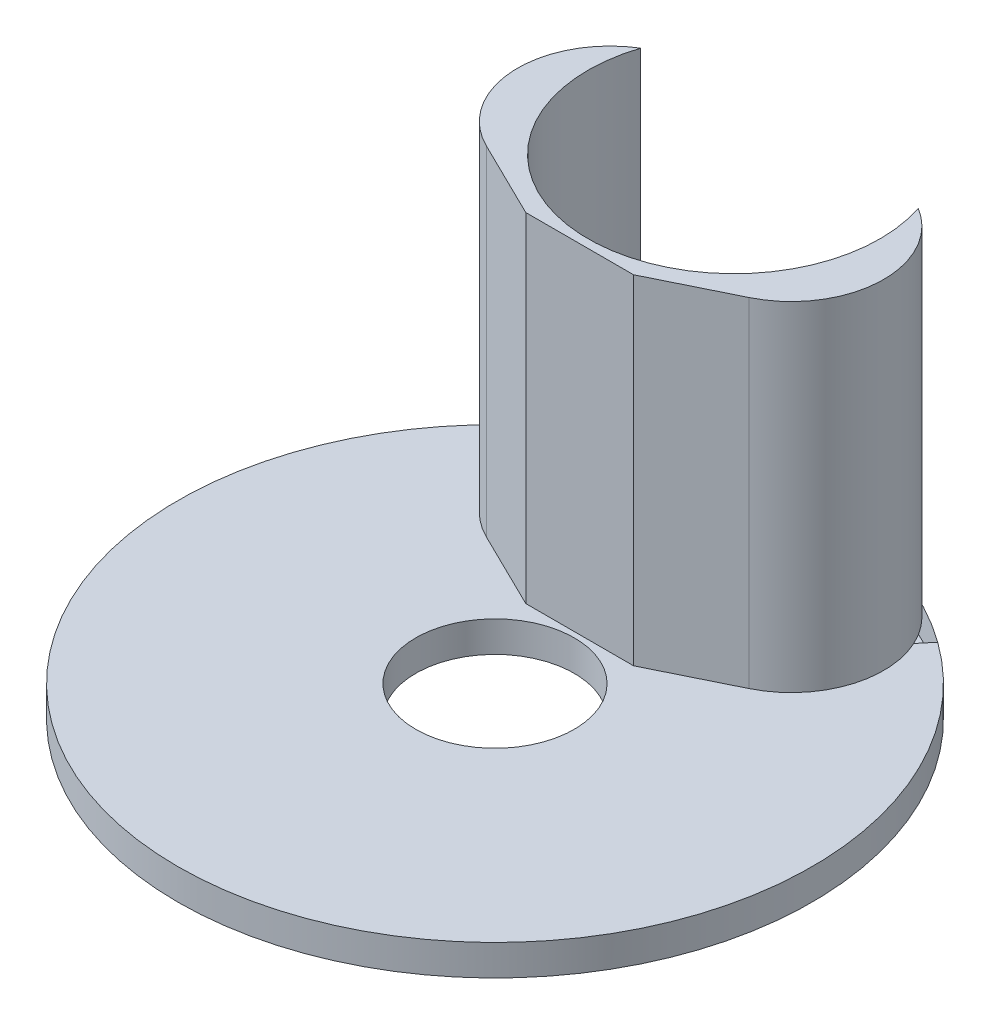
SolidWorks part; units mm, degrees
ref_plane "Front Plane" through (0, 0, 0) normal (0, 0, 1) x (1, 0, 0)
ref_plane "Top Plane" through (0, 0, 0) normal (0, 1, 0) x (1, 0, 0)
ref_plane "Right Plane" through (0, 0, 0) normal (1, 0, 0) x (0, 0, -1)
sketch "Sketch1" plane through (0, 0, 0) normal (0, 1, 0) x (1, 0, 0)
  circle A0 centre (0, 0) radius 20.6
  dimension "D1" = 41.2
extrude "Boss-Extrude1" add sketch "Sketch1" along normal blind 2
sketch "Sketch2" plane through (0, 2, 0) normal (0, 1, 0) x (1, 0, 0)
  circle A0 centre (0, 0) radius 5.15
  dimension "D1" = 10.3
extrude "Cut-Extrude1" cut sketch "Sketch2" against normal blind 3
sketch "Sketch3" plane through (0, 2, 0) normal (0, 1, 0) x (1, 0, 0)
  circle A0 centre (0, 13) radius 6.5
  dimension "D2" = 13
  dimension "D1" = 13
extrude "Cut-Extrude2" cut sketch "Sketch3" against normal blind 2
sketch "Sketch4" plane through (0, 2, 0) normal (0, 1, 0) x (1, 0, 0)
  line L0 (-3.5, 5.5) -> (-16.744, 12)
  line L1 (3.5, 5.5) -> (16.744, 12)
  line L4 (-3.5, 5.5) -> (3.5, 5.5)
  arc A0 (-16.744, 12) -> (-9, 18.53) centre (0, 0) cw
  circle A1 centre (0, 0) radius 20.6 construction
  arc A4 (9, 18.53) -> (16.744, 12) centre (0, 0) cw
  arc A6 (-9, 18.53) -> (9, 18.53) centre (0, 15.5297) ccw
  circle M8 centre (0, 0) radius 20.6
  dimension "D1" = 12
  dimension "D2" = 12
  dimension "D3" = 5.5
  dimension "D4" = 5.5
  dimension "D5" = 3.5
  dimension "D6" = 3.5
  dimension "D7" = 9
  dimension "D8" = 9
extrude "Boss-Extrude4" add sketch "Sketch4" along normal blind 22 contours L0 L4 L1 M8 region at (-9.9637, 2, -9.0726)
fillet "Fillet2" radius 6 2 edges at (16.744, 13, -12) (-16.744, 13, -12)
